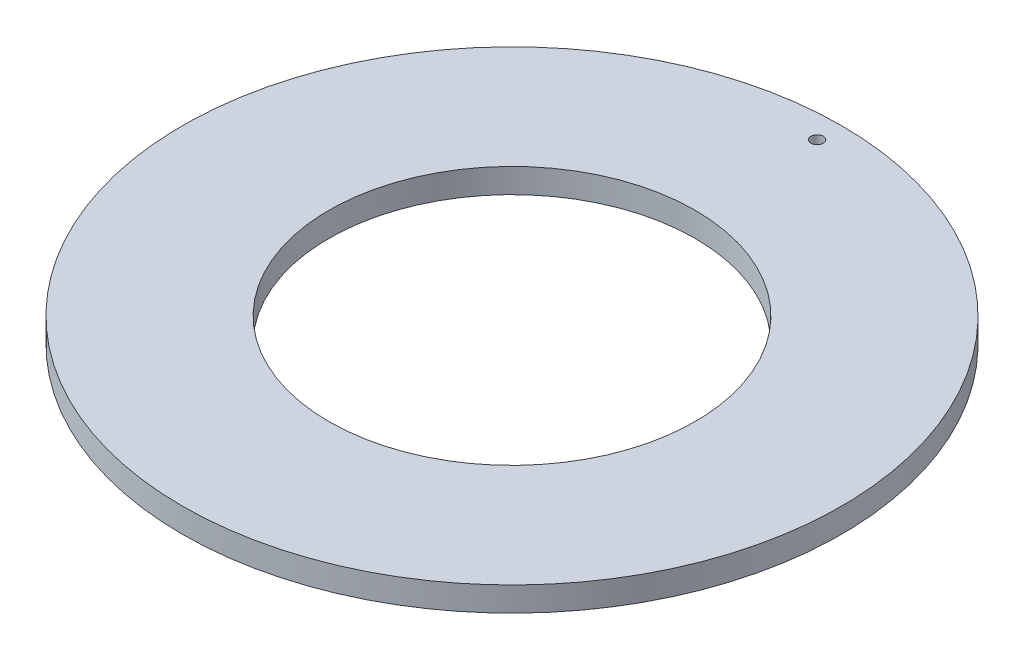
SolidWorks part; units mm, degrees
material "1060 Alloy"
ref_plane "Front Plane" through (0, 0, 0) normal (0, 0, 1) x (1, 0, 0)
ref_plane "Top Plane" through (0, 0, 0) normal (0, 1, 0) x (1, 0, 0)
ref_plane "Right Plane" through (0, 0, 0) normal (1, 0, 0) x (0, 0, -1)
sketch "Sketch1" plane through (0, 0, 0) normal (0, 1, 0) x (1, 0, 0)
  circle A0 centre (0, 0) radius 13.5
  dimension "D1" = 27
extrude "Boss-Extrude1" add sketch "Sketch1" along normal blind 1
sketch "Sketch4" plane through (0, 1, 0) normal (0, 1, 0) x (1, 0, 0)
  circle A0 centre (0, 12.5) radius 0.25
  circle A1 centre (0, 0) radius 7.5
  dimension "D1" = 0.5
  dimension "D3" = 15
  dimension "D2" = 12.5
extrude "Cut-Extrude3" cut sketch "Sketch4" against normal through all both and the other way through all
